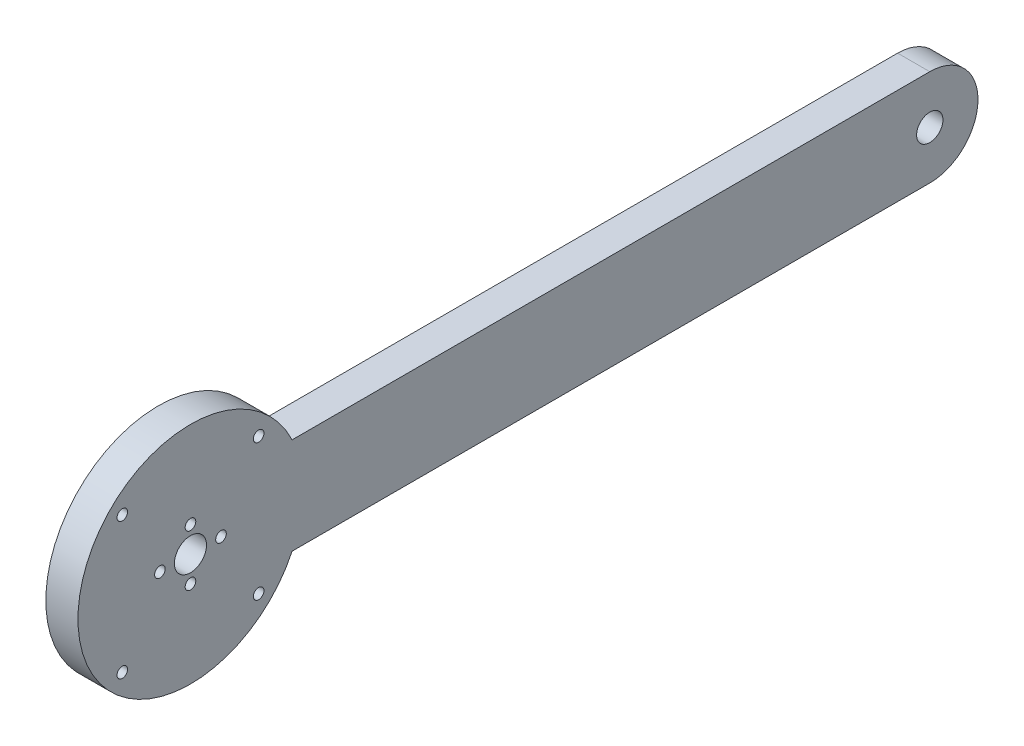
SolidWorks part; units mm, degrees
ref_plane "Front Plane" through (0, 0, 0) normal (1, 0, 0) x (0, 1, 0)
ref_plane "Top Plane" through (0, 0, 0) normal (0, 0, 1) x (0, 1, 0)
ref_plane "Right Plane" through (0, 0, 0) normal (0, 1, 0) x (-1, 0, 0)
sketch "Sketch1" plane through (0, 0, 0) normal (1, 0, 0) x (0, 1, 0)
  line L0 (-15, 0) -> (-15, 230)
  line L1 (15, 0) -> (15, 230)
  arc A0 (15, 0) -> (-15, 0) centre (0, 0) cw
  arc A1 (15, 230) -> (-15, 230) centre (0, 230) ccw
  dimension "D1" = 15
  dimension "D2" = 230
extrude "Boss-Extrude1" add sketch "Sketch1" along normal blind 10
sketch "Sketch2" plane through (10, 0, 0) normal (1, 0, 0) x (0, 1, 0)
  circle A0 centre (0, 0) radius 4.1
  dimension "D1" = 8.2
extrude "Cut-Extrude1" cut sketch "Sketch2" against normal through all
sketch "Sketch3" plane through (10, 0, 0) normal (1, 0, 0) x (0, 1, 0)
  line L0 (-8, 230) -> (8, 230) construction
  line L1 (0, 239.5) -> (0, 220.5) construction
  circle A0 centre (0, 239.5) radius 1.5
  circle A1 centre (8, 230) radius 1.5
  circle A2 centre (-8, 230) radius 1.5
  circle A3 centre (0, 220.5) radius 1.5
  arc A4 (15, 230) -> (-15, 230) centre (0, 230) ccw construction
  point P11 (0, 245)
  point P13 (0, 230)
  point P14 (0, 230)
  dimension "D1" = 3
  dimension "D2" = 16
  dimension "D3" = 19
extrude "Cut-Extrude2" cut sketch "Sketch3" against normal through all
sketch "Sketch4" plane through (10, 0, 0) normal (1, 0, 0) x (0, 1, 0)
  circle A0 centre (0, 230) radius 5
  arc A2 (15, 230) -> (-15, 230) centre (0, 230) ccw construction
  point P11 (0, 245)
  dimension "D1" = 10
extrude "Cut-Extrude3" cut sketch "Sketch4" against normal through all
sketch "Sketch5" plane through (10, 0, 0) normal (1, 0, 0) x (0, 1, 0)
  circle A0 centre (0, 230) radius 15
  arc A1 (15, 230) -> (-15, 230) centre (0, 230) ccw construction
  circle A2 centre (0, 230) radius 35
  dimension "D1" = 70
extrude "Boss-Extrude2" add sketch "Sketch5" against normal blind 10
sketch "Sketch6" plane through (10, 0, 0) normal (1, 0, 0) x (0, 1, 0)
  line L0 (-21.2132, 251.2132) -> (21.2132, 208.7868) construction
  line L1 (-21.2132, 208.7868) -> (21.2132, 251.2132) construction
  line L2 (-21.2132, 251.2132) -> (-21.2132, 208.7868) construction
  line L3 (-21.2132, 208.7868) -> (21.2132, 208.7868) construction
  circle A0 centre (-21.2132, 251.2132) radius 1.65
  circle A1 centre (21.2132, 251.2132) radius 1.65
  circle A2 centre (21.2132, 208.7868) radius 1.65
  circle A3 centre (-21.2132, 208.7868) radius 1.65
  circle A4 centre (0, 230) radius 5 construction
  point P8 (0, 230)
  dimension "D1" = 3.3
  dimension "D2" = 60
  dimension "D3" = 60
extrude "Cut-Extrude4" cut sketch "Sketch6" against normal through all
chamfer "Chamfer3" distance 1.5 angle 45 4 edges at (0, 0, 238) (0, -8, 228.5) (0, 0, 219) (0, 8, 228.5)
sketch "Sketch7" plane through (0, 0, 0) normal (-1, 0, 0) x (0, -1, 0)
  circle A0 centre (0, 239.5) radius 1.65
  circle A1 centre (8, 230) radius 1.65
  circle A2 centre (0, 220.5) radius 1.65
  circle A3 centre (-8, 230) radius 1.65
  dimension "D1" = 3.3
extrude "Cut-Extrude5" cut sketch "Sketch7" against normal through all
